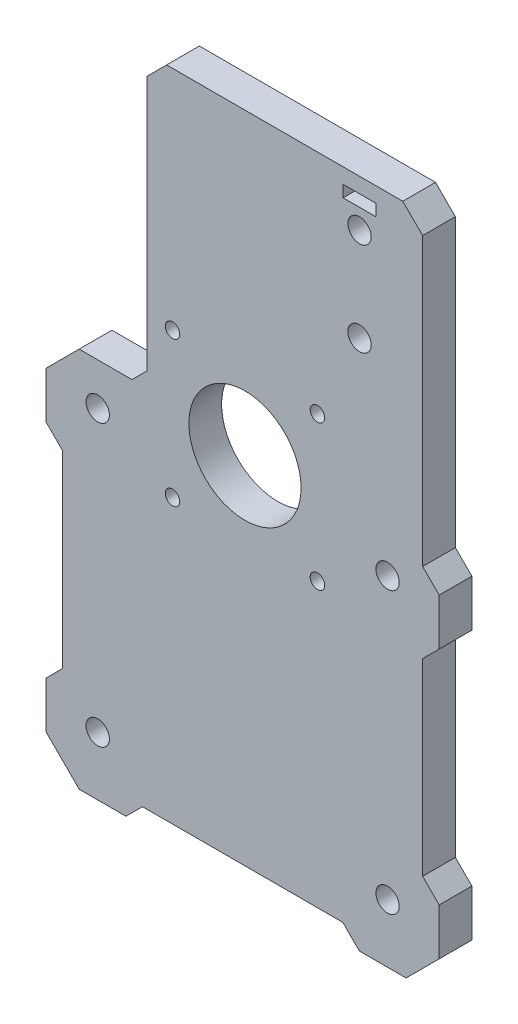
SolidWorks part; units mm, degrees
ref_plane "Alzado" through (0, 0, 0) normal (0, 0, 1) x (1, 0, 0)
ref_plane "Planta" through (0, 0, 0) normal (0, 1, 0) x (1, 0, 0)
ref_plane "Vista lateral" through (0, 0, 0) normal (1, 0, 0) x (0, 0, -1)
sketch "Croquis1" plane through (0, 0, 0) normal (0, 0, 1) x (1, 0, 0)
  line L0 (0, 0) -> (0, 36.5) construction
  line L5 (31, 30) -> (-31, 30)
  line L10 (31, 30) -> (31, -30)
  line L11 (31, -30) -> (-31, -30)
  line L12 (-31, 30) -> (-31, -30)
  line L13 (31, 30) -> (-31, -30) construction
  line L14 (31, -30) -> (-31, 30) construction
  line L15 (-38.5, 39) -> (-20.5, 39)
  line L16 (-38.5, 39) -> (-38.5, -39)
  line L17 (-38.5, -39) -> (38.5, -39)
  line L18 (38.5, 39) -> (38.5, -39)
  line L19 (-38.5, 39) -> (38.5, -39) construction
  line L20 (-38.5, -39) -> (38.5, 39) construction
  line L21 (38.5, 39) -> (38.5, 96.7574)
  line L26 (34.2574, 101) -> (-16.2574, 101)
  line L27 (-20.5, 96.7574) -> (-20.5, 39)
  line L28 (34.2574, 101) -> (38.5, 96.7574)
  line L29 (-16.2574, 101) -> (-20.5, 96.7574)
  circle A0 centre (-31, 30) radius 2.5
  circle A1 centre (31, 30) radius 2.5
  circle A2 centre (31, -30) radius 2.5
  circle A3 centre (-31, -30) radius 2.5
  point P0 (0, 0)
  point P5 (0, 0)
  dimension "D5" = 36.5
  dimension "D6" = 62
  dimension "D1" = 62
  dimension "D2" = 60
  dimension "D3" = 78
  dimension "D4" = 77
  dimension "D7" = 59
  dimension "D8" = 135
  dimension "D9" = 6
  dimension "D10" = 45
  dimension "D11" = 6
extrude "FormaBase" add sketch "Croquis1" along normal blind 7 contours L26 L29 L27 L15 L16 L17 L18 L21 L28 A3 L12 A0 L5 A1 L10 A2 L11 | A3 L11 A2 L10 A1 L5 A0 L12 region at (0, 0, 0) region at (5.5837, 43.3379, 0)
sketch "Croquis9" plane through (0, 0, 7) normal (0, 0, 1) x (1, 0, 0)
  line L0 (21.4289, -39) -> (24.9645, -42.5355)
  line L1 (-38.5, -39) -> (38.5, -39) construction
  line L2 (24.9645, -42.5355) -> (34.9645, -42.5355)
  line L3 (34.9645, -42.5355) -> (42.0355, -35.4645)
  line L4 (42.0355, -35.4645) -> (42.0355, -25.4645)
  line L5 (42.0355, -25.4645) -> (38.5, -21.9289)
  line L6 (38.5, 96.7574) -> (38.5, -39) construction
  line L7 (0, -55) -> (0, 55) construction
  line L8 (-42.0355, -25.4645) -> (-38.5, -21.9289)
  line L9 (-42.0355, -35.4645) -> (-42.0355, -25.4645)
  line L10 (-34.9645, -42.5355) -> (-42.0355, -35.4645)
  line L11 (-24.9645, -42.5355) -> (-34.9645, -42.5355)
  line L12 (-21.4289, -39) -> (-24.9645, -42.5355)
  line L13 (-38.5, -21.9289) -> (-38.5, -30.4645)
  line L14 (-29.9645, -39) -> (-21.4289, -39)
  line L15 (-29.9645, -39) -> (-38.5, -30.4645)
  line L16 (38.5, -21.9289) -> (38.5, -30.4645)
  line L17 (29.9645, -39) -> (21.4289, -39)
  line L18 (29.9645, -39) -> (38.5, -30.4645)
  line L19 (-38.5, 39) -> (-20.5, 39) construction
  line L21 (-23.668, 39) -> (-20.1325, 42.5355)
  line L22 (-34.9645, 39) -> (-42.0355, 31.9289)
  line L23 (-42.0355, 31.9289) -> (-42.0355, 21.9289)
  line L24 (-42.0355, 21.9289) -> (-38.5, 18.3934)
  line L25 (-38.5, 39) -> (-38.5, -39) construction
  line L26 (42.0355, 21.9289) -> (38.5, 18.3934)
  line L27 (42.0355, 31.9289) -> (42.0355, 21.9289)
  line L28 (34.9645, 39) -> (42.0355, 31.9289)
  line L29 (-34.9645, 39) -> (-38.5, 18.3934)
  line L30 (38.5, 18.3934) -> (34.9645, 39)
  line M29 (-20.5, 96.7574) -> (-20.5, 39)
  line M30 (-20.5, 39) -> (-38.5, 39)
  line M31 (-38.5, 39) -> (-38.5, -39)
  line M32 (-38.5, -39) -> (38.5, -39)
  line M33 (38.5, -39) -> (38.5, 96.7574)
  dimension "D1" = 45
  dimension "D2" = 45
  dimension "D3" = 10
  dimension "D4" = 10
  dimension "D5" = 10
  dimension "D6" = 5
  dimension "D7" = 5
  dimension "D8" = 45
  dimension "D10" = 10
  dimension "D12" = 10
  dimension "D13" = 135
  dimension "D14" = 5
extrude "Detalles" add sketch "Croquis9" against normal through all contours L29 L22 M31 | L23 L24 L22 M31 | L30 L28 M33 | L28 L26 L27 M33 | L4 L5 L3 M33 | L2 L3 L0 M32 | L18 M32 M33 | L10 L8 L9 M31 | L15 M32 M31 | L12 L10 L11 M32 | L21 M30 M29 region at (29.9645, -40.6139, 7) region at (37.3215, 30.9526, 7) region at (40.1139, 26.9289, 7) region at (-21.556, 40.056, 7) region at (-40.1139, 26.9289, 7) region at (-37.3215, 30.9526, 7) region at (-29.9645, -40.6139, 7) region at (35.6548, -36.1548, 7) region at (40.1139, -30.4645, 7) region at (-35.6548, -36.1548, 7) region at (-40.1139, -30.4645, 7)
sketch "Croquis10" plane through (0, 0, 7) normal (0, 0, 1) x (1, 0, 0)
  line L0 (-38.5, 35.4645) -> (-34.9645, 39)
  line L1 (-38.5, 39) -> (-23.668, 39) construction
  line L2 (-34.9645, 39) -> (-38.5, 39)
  line L3 (-38.5, 39) -> (-38.5, 35.4645)
  line L4 (38.5, 91) -> (25, 91) construction
  line L5 (38.5, 96.7574) -> (38.5, 35.4645) construction
  line L6 (34.2574, 101) -> (-16.2574, 101) construction
  line L7 (-38.5, 18.3934) -> (-38.5, -21.9289) construction
  line L8 (-21.4289, -39) -> (21.4289, -39) construction
  line L14 (16, 21.5) -> (-15, 21.5)
  line L15 (16, 21.5) -> (16, 52.5)
  line L16 (16, 52.5) -> (-15, 52.5)
  line L17 (-15, 21.5) -> (-15, 52.5)
  line L18 (16, 21.5) -> (-15, 52.5) construction
  line L19 (16, 52.5) -> (-15, 21.5) construction
  circle A0 centre (25, 91) radius 2.5
  circle A1 centre (-15, 52.5) radius 1.55
  circle A2 centre (25, 71) radius 2.5
  circle A3 centre (0.5, 37) radius 12
  circle A8 centre (16, 52.5) radius 1.55
  circle A9 centre (16, 21.5) radius 1.55
  circle A10 centre (-15, 21.5) radius 1.55
  point P36 (0.5, 37)
  line M22 (-23.668, 39) -> (-38.5, 39)
  line M23 (-38.5, 39) -> (-38.5, 35.4645)
  dimension "D1" = 13.5
  dimension "D2" = 5
  dimension "D3" = 10
  dimension "D5" = 24
  dimension "D8" = 3.1
  dimension "D6" = 39
  dimension "D7" = 76
  dimension "D9" = 4
  dimension "D10" = 20
  dimension "D11" = 31
  dimension "D4" = 2
extrude "BarrenosNEMA" cut sketch "Croquis10" against normal through all contours L0 M23 M22 | A2 | A0 | A3 | A1 | A8 | A9 | A10 region at (-37.3215, 37.8215, 7) region at (25, 91, 7) region at (25, 71, 7) region at (0.5, 37, 7)
sketch "Croquis11" plane through (0, 0, 7) normal (0, 0, 1) x (1, 0, 0)
  line L0 (25, 91) -> (25, 96.5) construction
  line L2 (21.5, 97.75) -> (28.5, 97.75)
  line L3 (21.5, 97.75) -> (21.5, 95.25)
  line L4 (21.5, 95.25) -> (28.5, 95.25)
  line L5 (28.5, 97.75) -> (28.5, 95.25)
  line L6 (21.5, 97.75) -> (28.5, 95.25) construction
  line L7 (21.5, 95.25) -> (28.5, 97.75) construction
  dimension "D1" = 5.5
  dimension "D2" = 7
  dimension "D3" = 2.5
extrude "EspacioCadena" cut sketch "Croquis11" against normal blind 10
